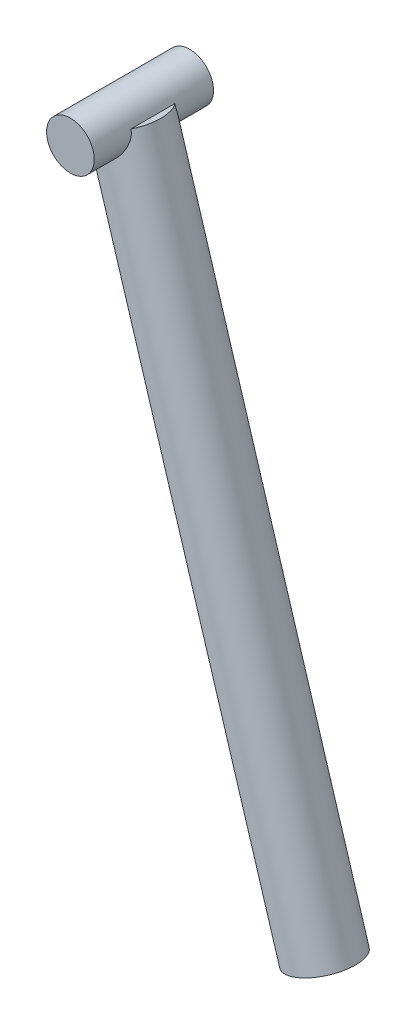
SolidWorks part; units mm, degrees
material "Acero aleado"
ref_plane "Alzado" through (0, 0, 0) normal (0, 0, 1) x (1, 0, 0)
ref_plane "Planta" through (0, 0, 0) normal (0, 1, 0) x (1, 0, 0)
ref_plane "Vista lateral" through (0, 0, 0) normal (1, 0, 0) x (0, 0, -1)
sketch3d "Sk_Tubo_tija"
  line L0 (-115.633, 378.2185, 0) -> (-197.1657, 644.9, 0)
  dimension "D1" = 278.8666
sweep "Tubo_tija" add path "Sk_Tubo_tija" circular profile diameter 27.2 parameters "D3"=27.2
sketch3d "Sk_Cabeza"
  line L0 (-197.1657, 644.9, -25) -> (-197.1657, 644.9, 25)
sweep "Cabeza" add path "Sk_Cabeza" circular profile diameter 20 parameters "D3"=20
